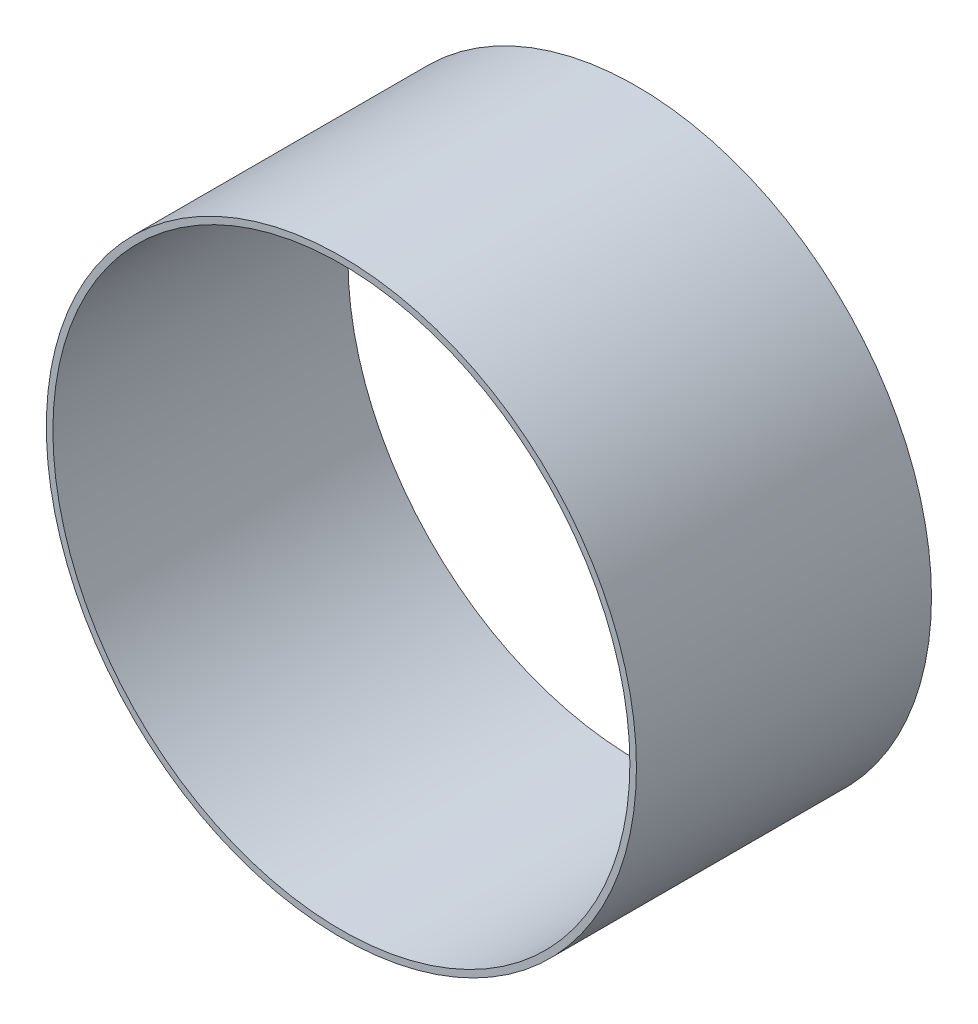
SolidWorks part; units mm, degrees
material "E-Glass Fiber"
ref_plane "Front Plane" through (0, 0, 0) normal (0, 0, 1) x (1, 0, 0)
ref_plane "Top Plane" through (0, 0, 0) normal (0, 1, 0) x (1, 0, 0)
ref_plane "Right Plane" through (0, 0, 0) normal (1, 0, 0) x (0, 0, -1)
sketch "Sketch1" plane through (0, 0, 0) normal (0, 0, 1) x (1, 0, 0)
  circle A0 centre (0, 0) radius 50.8
  circle A1 centre (0, 0) radius 49.6697
  dimension "D1" = 101.6
  dimension "D2" = 99.3394
extrude "Boss-Extrude1" add sketch "Sketch1" along normal blind 50.8
